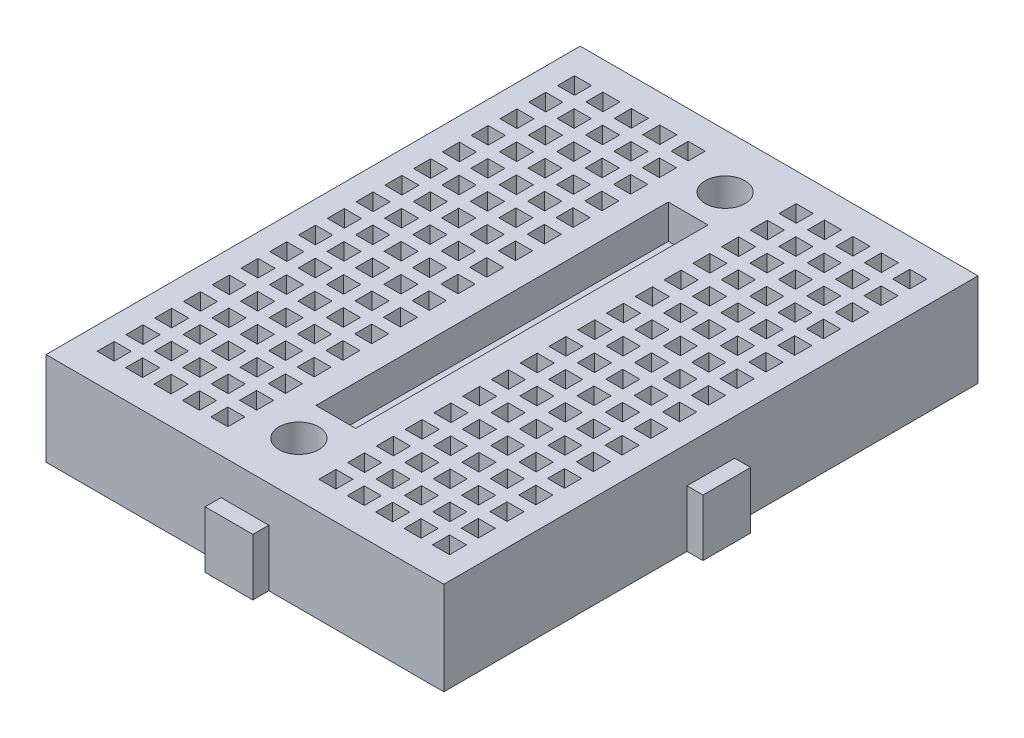
SolidWorks part; units mm, degrees
ref_plane "Front Plane" through (0, 0, 0) normal (0, 0, 1) x (1, 0, 0)
ref_plane "Top Plane" through (0, 0, 0) normal (0, 1, 0) x (1, 0, 0)
ref_plane "Right Plane" through (0, 0, 0) normal (1, 0, 0) x (0, 0, -1)
sketch "Sketch2" plane through (0, 0, 0) normal (0, 1, 0) x (1, 0, 0)
  line L1 (0, 23.5) -> (-17.5, 23.5)
  line L2 (0, 23.5) -> (0, -23.5)
  line L3 (0, -23.5) -> (-17.5, -23.5)
  line L4 (-17.5, 23.5) -> (-17.5, -23.5)
  line L5 (0, 23.5) -> (-17.5, -23.5) construction
  line L6 (0, -23.5) -> (-17.5, 23.5) construction
  point P0 (0, 0)
  point P7 (0, 0)
  dimension "D1" = 17.5
  dimension "D2" = 47
extrude "Boss-Extrude1" add sketch "Sketch2" along normal blind 5.2
sketch "Sketch3" plane through (0, 5.2, 0) normal (0, 1, 0) x (1, 0, 0)
  line L0 (0, -23.5) -> (0, 23.5) construction
  line L5 (1.75, -15.5) -> (-1.75, -15.5)
  line L6 (1.75, -15.5) -> (1.75, 15.5)
  line L7 (0, 23.5) -> (-17.5, 23.5) construction
  line L8 (-17.5, -23.5) -> (0, -23.5) construction
  line L9 (1.75, 15.5) -> (-1.75, 15.5)
  line L10 (-1.75, -15.5) -> (-1.75, 15.5)
  line L12 (-13, 21) -> (-13, 19.5)
  line L13 (-15.5, 21) -> (-14, 21)
  line L14 (-15.5, 21) -> (-15.5, 19.5)
  line L15 (-15.5, 19.5) -> (-14, 19.5)
  line L16 (-14, 21) -> (-14, 19.5)
  line L17 (-13, 21) -> (-11.5, 21)
  line L18 (-11.5, 21) -> (-11.5, 19.5)
  line L19 (-13, 19.5) -> (-11.5, 19.5)
  line L20 (-10.5, 21) -> (-10.5, 19.5)
  line L21 (-10.5, 21) -> (-9, 21)
  line L22 (-9, 21) -> (-9, 19.5)
  line L23 (-10.5, 19.5) -> (-9, 19.5)
  line L24 (-8, 21) -> (-8, 19.5)
  line L25 (-8, 21) -> (-6.5, 21)
  line L26 (-6.5, 21) -> (-6.5, 19.5)
  line L27 (-8, 19.5) -> (-6.5, 19.5)
  line L28 (-5.5, 21) -> (-5.5, 19.5)
  line L29 (-5.5, 21) -> (-4, 21)
  line L30 (-4, 21) -> (-4, 19.5)
  line L31 (-5.5, 19.5) -> (-4, 19.5)
  line L32 (-13, 18.4688) -> (-13, 16.9687)
  line L33 (-13, 18.4688) -> (-11.5, 18.4688)
  line L34 (-11.5, 18.4688) -> (-11.5, 16.9687)
  line L35 (-13, 16.9687) -> (-11.5, 16.9687)
  line L36 (-10.5, 18.4688) -> (-10.5, 16.9687)
  line L37 (-10.5, 18.4688) -> (-9, 18.4688)
  line L38 (-9, 18.4688) -> (-9, 16.9687)
  line L39 (-10.5, 16.9687) -> (-9, 16.9687)
  line L40 (-8, 18.4688) -> (-8, 16.9687)
  line L41 (-8, 18.4688) -> (-6.5, 18.4688)
  line L42 (-6.5, 18.4688) -> (-6.5, 16.9687)
  line L43 (-8, 16.9687) -> (-6.5, 16.9687)
  line L44 (-5.5, 18.4688) -> (-5.5, 16.9687)
  line L45 (-5.5, 18.4688) -> (-4, 18.4688)
  line L46 (-4, 18.4688) -> (-4, 16.9687)
  line L47 (-5.5, 16.9687) -> (-4, 16.9687)
  line L48 (-13, 15.9375) -> (-13, 14.4375)
  line L49 (-13, 15.9375) -> (-11.5, 15.9375)
  line L50 (-11.5, 15.9375) -> (-11.5, 14.4375)
  line L51 (-13, 14.4375) -> (-11.5, 14.4375)
  line L52 (-10.5, 15.9375) -> (-10.5, 14.4375)
  line L53 (-10.5, 15.9375) -> (-9, 15.9375)
  line L54 (-9, 15.9375) -> (-9, 14.4375)
  line L55 (-10.5, 14.4375) -> (-9, 14.4375)
  line L56 (-8, 15.9375) -> (-8, 14.4375)
  line L57 (-8, 15.9375) -> (-6.5, 15.9375)
  line L58 (-6.5, 15.9375) -> (-6.5, 14.4375)
  line L59 (-8, 14.4375) -> (-6.5, 14.4375)
  line L60 (-5.5, 15.9375) -> (-5.5, 14.4375)
  line L61 (-5.5, 15.9375) -> (-4, 15.9375)
  line L62 (-4, 15.9375) -> (-4, 14.4375)
  line L63 (-5.5, 14.4375) -> (-4, 14.4375)
  line L64 (-13, 13.4063) -> (-13, 11.9062)
  line L65 (-13, 13.4063) -> (-11.5, 13.4063)
  line L66 (-11.5, 13.4063) -> (-11.5, 11.9062)
  line L67 (-13, 11.9062) -> (-11.5, 11.9062)
  line L68 (-10.5, 13.4063) -> (-10.5, 11.9062)
  line L69 (-10.5, 13.4063) -> (-9, 13.4063)
  line L70 (-9, 13.4063) -> (-9, 11.9062)
  line L71 (-10.5, 11.9062) -> (-9, 11.9062)
  line L72 (-8, 13.4063) -> (-8, 11.9062)
  line L73 (-8, 13.4063) -> (-6.5, 13.4063)
  line L74 (-6.5, 13.4063) -> (-6.5, 11.9062)
  line L75 (-8, 11.9062) -> (-6.5, 11.9062)
  line L76 (-5.5, 13.4063) -> (-5.5, 11.9062)
  line L77 (-5.5, 13.4063) -> (-4, 13.4063)
  line L78 (-4, 13.4063) -> (-4, 11.9062)
  line L79 (-5.5, 11.9062) -> (-4, 11.9062)
  line L80 (-13, 10.875) -> (-13, 9.375)
  line L81 (-13, 10.875) -> (-11.5, 10.875)
  line L82 (-11.5, 10.875) -> (-11.5, 9.375)
  line L83 (-13, 9.375) -> (-11.5, 9.375)
  line L84 (-10.5, 10.875) -> (-10.5, 9.375)
  line L85 (-10.5, 10.875) -> (-9, 10.875)
  line L86 (-9, 10.875) -> (-9, 9.375)
  line L87 (-10.5, 9.375) -> (-9, 9.375)
  line L88 (-8, 10.875) -> (-8, 9.375)
  line L89 (-8, 10.875) -> (-6.5, 10.875)
  line L90 (-6.5, 10.875) -> (-6.5, 9.375)
  line L91 (-8, 9.375) -> (-6.5, 9.375)
  line L92 (-5.5, 10.875) -> (-5.5, 9.375)
  line L93 (-5.5, 10.875) -> (-4, 10.875)
  line L94 (-4, 10.875) -> (-4, 9.375)
  line L95 (-5.5, 9.375) -> (-4, 9.375)
  line L96 (-13, 8.3438) -> (-13, 6.8438)
  line L97 (-13, 8.3438) -> (-11.5, 8.3438)
  line L98 (-11.5, 8.3438) -> (-11.5, 6.8438)
  line L99 (-13, 6.8438) -> (-11.5, 6.8438)
  line L100 (-10.5, 8.3438) -> (-10.5, 6.8438)
  line L101 (-10.5, 8.3438) -> (-9, 8.3438)
  line L102 (-9, 8.3438) -> (-9, 6.8438)
  line L103 (-10.5, 6.8438) -> (-9, 6.8438)
  line L104 (-8, 8.3438) -> (-8, 6.8438)
  line L105 (-8, 8.3438) -> (-6.5, 8.3438)
  line L106 (-6.5, 8.3438) -> (-6.5, 6.8438)
  line L107 (-8, 6.8438) -> (-6.5, 6.8438)
  line L108 (-5.5, 8.3438) -> (-5.5, 6.8438)
  line L109 (-5.5, 8.3438) -> (-4, 8.3438)
  line L110 (-4, 8.3438) -> (-4, 6.8438)
  line L111 (-5.5, 6.8438) -> (-4, 6.8438)
  line L112 (-13, 5.8125) -> (-13, 4.3125)
  line L113 (-13, 5.8125) -> (-11.5, 5.8125)
  line L114 (-11.5, 5.8125) -> (-11.5, 4.3125)
  line L115 (-13, 4.3125) -> (-11.5, 4.3125)
  line L116 (-10.5, 5.8125) -> (-10.5, 4.3125)
  line L117 (-10.5, 5.8125) -> (-9, 5.8125)
  line L118 (-9, 5.8125) -> (-9, 4.3125)
  line L119 (-10.5, 4.3125) -> (-9, 4.3125)
  line L120 (-8, 5.8125) -> (-8, 4.3125)
  line L121 (-8, 5.8125) -> (-6.5, 5.8125)
  line L122 (-6.5, 5.8125) -> (-6.5, 4.3125)
  line L123 (-8, 4.3125) -> (-6.5, 4.3125)
  line L124 (-5.5, 5.8125) -> (-5.5, 4.3125)
  line L125 (-5.5, 5.8125) -> (-4, 5.8125)
  line L126 (-4, 5.8125) -> (-4, 4.3125)
  line L127 (-5.5, 4.3125) -> (-4, 4.3125)
  line L128 (-13, 3.2813) -> (-13, 1.7813)
  line L129 (-13, 3.2813) -> (-11.5, 3.2813)
  line L130 (-11.5, 3.2813) -> (-11.5, 1.7813)
  line L131 (-13, 1.7813) -> (-11.5, 1.7813)
  line L132 (-10.5, 3.2813) -> (-10.5, 1.7813)
  line L133 (-10.5, 3.2813) -> (-9, 3.2813)
  line L134 (-9, 3.2813) -> (-9, 1.7813)
  line L135 (-10.5, 1.7813) -> (-9, 1.7813)
  line L136 (-8, 3.2813) -> (-8, 1.7813)
  line L137 (-8, 3.2813) -> (-6.5, 3.2813)
  line L138 (-6.5, 3.2813) -> (-6.5, 1.7813)
  line L139 (-8, 1.7813) -> (-6.5, 1.7813)
  line L140 (-5.5, 3.2813) -> (-5.5, 1.7813)
  line L141 (-5.5, 3.2813) -> (-4, 3.2813)
  line L142 (-4, 3.2813) -> (-4, 1.7813)
  line L143 (-5.5, 1.7813) -> (-4, 1.7813)
  line L144 (-13, 0.75) -> (-13, -0.75)
  line L145 (-13, 0.75) -> (-11.5, 0.75)
  line L146 (-11.5, 0.75) -> (-11.5, -0.75)
  line L147 (-13, -0.75) -> (-11.5, -0.75)
  line L148 (-10.5, 0.75) -> (-10.5, -0.75)
  line L149 (-10.5, 0.75) -> (-9, 0.75)
  line L150 (-9, 0.75) -> (-9, -0.75)
  line L151 (-10.5, -0.75) -> (-9, -0.75)
  line L152 (-8, 0.75) -> (-8, -0.75)
  line L153 (-8, 0.75) -> (-6.5, 0.75)
  line L154 (-6.5, 0.75) -> (-6.5, -0.75)
  line L155 (-8, -0.75) -> (-6.5, -0.75)
  line L156 (-5.5, 0.75) -> (-5.5, -0.75)
  line L157 (-5.5, 0.75) -> (-4, 0.75)
  line L158 (-4, 0.75) -> (-4, -0.75)
  line L159 (-5.5, -0.75) -> (-4, -0.75)
  line L160 (-13, -1.7812) -> (-13, -3.2812)
  line L161 (-13, -1.7812) -> (-11.5, -1.7812)
  line L162 (-11.5, -1.7812) -> (-11.5, -3.2812)
  line L163 (-13, -3.2812) -> (-11.5, -3.2812)
  line L164 (-10.5, -1.7812) -> (-10.5, -3.2812)
  line L165 (-10.5, -1.7812) -> (-9, -1.7812)
  line L166 (-9, -1.7812) -> (-9, -3.2812)
  line L167 (-10.5, -3.2812) -> (-9, -3.2812)
  line L168 (-8, -1.7812) -> (-8, -3.2812)
  line L169 (-8, -1.7812) -> (-6.5, -1.7812)
  line L170 (-6.5, -1.7812) -> (-6.5, -3.2812)
  line L171 (-8, -3.2812) -> (-6.5, -3.2812)
  line L172 (-5.5, -1.7812) -> (-5.5, -3.2812)
  line L173 (-5.5, -1.7812) -> (-4, -1.7812)
  line L174 (-4, -1.7812) -> (-4, -3.2812)
  line L175 (-5.5, -3.2812) -> (-4, -3.2812)
  line L176 (-13, -4.3125) -> (-13, -5.8125)
  line L177 (-13, -4.3125) -> (-11.5, -4.3125)
  line L178 (-11.5, -4.3125) -> (-11.5, -5.8125)
  line L179 (-13, -5.8125) -> (-11.5, -5.8125)
  line L180 (-10.5, -4.3125) -> (-10.5, -5.8125)
  line L181 (-10.5, -4.3125) -> (-9, -4.3125)
  line L182 (-9, -4.3125) -> (-9, -5.8125)
  line L183 (-10.5, -5.8125) -> (-9, -5.8125)
  line L184 (-8, -4.3125) -> (-8, -5.8125)
  line L185 (-8, -4.3125) -> (-6.5, -4.3125)
  line L186 (-6.5, -4.3125) -> (-6.5, -5.8125)
  line L187 (-8, -5.8125) -> (-6.5, -5.8125)
  line L188 (-5.5, -4.3125) -> (-5.5, -5.8125)
  line L189 (-5.5, -4.3125) -> (-4, -4.3125)
  line L190 (-4, -4.3125) -> (-4, -5.8125)
  line L191 (-5.5, -5.8125) -> (-4, -5.8125)
  line L192 (-13, -6.8437) -> (-13, -8.3437)
  line L193 (-13, -6.8437) -> (-11.5, -6.8437)
  line L194 (-11.5, -6.8437) -> (-11.5, -8.3437)
  line L195 (-13, -8.3437) -> (-11.5, -8.3437)
  line L196 (-10.5, -6.8437) -> (-10.5, -8.3437)
  line L197 (-10.5, -6.8437) -> (-9, -6.8437)
  line L198 (-9, -6.8437) -> (-9, -8.3437)
  line L199 (-10.5, -8.3437) -> (-9, -8.3437)
  line L200 (-8, -6.8437) -> (-8, -8.3437)
  line L201 (-8, -6.8437) -> (-6.5, -6.8437)
  line L202 (-6.5, -6.8437) -> (-6.5, -8.3437)
  line L203 (-8, -8.3437) -> (-6.5, -8.3437)
  line L204 (-5.5, -6.8437) -> (-5.5, -8.3437)
  line L205 (-5.5, -6.8437) -> (-4, -6.8437)
  line L206 (-4, -6.8437) -> (-4, -8.3437)
  line L207 (-5.5, -8.3437) -> (-4, -8.3437)
  line L208 (-13, -9.375) -> (-13, -10.875)
  line L209 (-13, -9.375) -> (-11.5, -9.375)
  line L210 (-11.5, -9.375) -> (-11.5, -10.875)
  line L211 (-13, -10.875) -> (-11.5, -10.875)
  line L212 (-10.5, -9.375) -> (-10.5, -10.875)
  line L213 (-10.5, -9.375) -> (-9, -9.375)
  line L214 (-9, -9.375) -> (-9, -10.875)
  line L215 (-10.5, -10.875) -> (-9, -10.875)
  line L216 (-8, -9.375) -> (-8, -10.875)
  line L217 (-8, -9.375) -> (-6.5, -9.375)
  line L218 (-6.5, -9.375) -> (-6.5, -10.875)
  line L219 (-8, -10.875) -> (-6.5, -10.875)
  line L220 (-5.5, -9.375) -> (-5.5, -10.875)
  line L221 (-5.5, -9.375) -> (-4, -9.375)
  line L222 (-4, -9.375) -> (-4, -10.875)
  line L223 (-5.5, -10.875) -> (-4, -10.875)
  line L224 (-13, -11.9062) -> (-13, -13.4062)
  line L225 (-13, -11.9062) -> (-11.5, -11.9062)
  line L226 (-11.5, -11.9062) -> (-11.5, -13.4062)
  line L227 (-13, -13.4062) -> (-11.5, -13.4062)
  line L228 (-10.5, -11.9062) -> (-10.5, -13.4062)
  line L229 (-10.5, -11.9062) -> (-9, -11.9062)
  line L230 (-9, -11.9062) -> (-9, -13.4062)
  line L231 (-10.5, -13.4062) -> (-9, -13.4062)
  line L232 (-8, -11.9062) -> (-8, -13.4062)
  line L233 (-8, -11.9062) -> (-6.5, -11.9062)
  line L234 (-6.5, -11.9062) -> (-6.5, -13.4062)
  line L235 (-8, -13.4062) -> (-6.5, -13.4062)
  line L236 (-5.5, -11.9062) -> (-5.5, -13.4062)
  line L237 (-5.5, -11.9062) -> (-4, -11.9062)
  line L238 (-4, -11.9062) -> (-4, -13.4062)
  line L239 (-5.5, -13.4062) -> (-4, -13.4062)
  line L240 (-13, -14.4375) -> (-13, -15.9375)
  line L241 (-13, -14.4375) -> (-11.5, -14.4375)
  line L242 (-11.5, -14.4375) -> (-11.5, -15.9375)
  line L243 (-13, -15.9375) -> (-11.5, -15.9375)
  line L244 (-10.5, -14.4375) -> (-10.5, -15.9375)
  line L245 (-10.5, -14.4375) -> (-9, -14.4375)
  line L246 (-9, -14.4375) -> (-9, -15.9375)
  line L247 (-10.5, -15.9375) -> (-9, -15.9375)
  line L248 (-8, -14.4375) -> (-8, -15.9375)
  line L249 (-8, -14.4375) -> (-6.5, -14.4375)
  line L250 (-6.5, -14.4375) -> (-6.5, -15.9375)
  line L251 (-8, -15.9375) -> (-6.5, -15.9375)
  line L252 (-5.5, -14.4375) -> (-5.5, -15.9375)
  line L253 (-5.5, -14.4375) -> (-4, -14.4375)
  line L254 (-4, -14.4375) -> (-4, -15.9375)
  line L255 (-5.5, -15.9375) -> (-4, -15.9375)
  line L256 (-13, -16.9687) -> (-13, -18.4687)
  line L257 (-13, -16.9687) -> (-11.5, -16.9687)
  line L258 (-11.5, -16.9687) -> (-11.5, -18.4687)
  line L259 (-13, -18.4687) -> (-11.5, -18.4687)
  line L260 (-10.5, -16.9687) -> (-10.5, -18.4687)
  line L261 (-10.5, -16.9687) -> (-9, -16.9687)
  line L262 (-9, -16.9687) -> (-9, -18.4687)
  line L263 (-10.5, -18.4687) -> (-9, -18.4687)
  line L264 (-8, -16.9687) -> (-8, -18.4687)
  line L265 (-8, -16.9687) -> (-6.5, -16.9687)
  line L266 (-6.5, -16.9687) -> (-6.5, -18.4687)
  line L267 (-8, -18.4687) -> (-6.5, -18.4687)
  line L268 (-5.5, -16.9687) -> (-5.5, -18.4687)
  line L269 (-5.5, -16.9687) -> (-4, -16.9687)
  line L270 (-4, -16.9687) -> (-4, -18.4687)
  line L271 (-5.5, -18.4687) -> (-4, -18.4687)
  line L272 (-13, -19.5) -> (-13, -21)
  line L273 (-13, -19.5) -> (-11.5, -19.5)
  line L274 (-11.5, -19.5) -> (-11.5, -21)
  line L275 (-13, -21) -> (-11.5, -21)
  line L276 (-10.5, -19.5) -> (-10.5, -21)
  line L277 (-10.5, -19.5) -> (-9, -19.5)
  line L278 (-9, -19.5) -> (-9, -21)
  line L279 (-10.5, -21) -> (-9, -21)
  line L280 (-8, -19.5) -> (-8, -21)
  line L281 (-8, -19.5) -> (-6.5, -19.5)
  line L282 (-6.5, -19.5) -> (-6.5, -21)
  line L283 (-8, -21) -> (-6.5, -21)
  line L284 (-5.5, -19.5) -> (-5.5, -21)
  line L285 (-5.5, -19.5) -> (-4, -19.5)
  line L286 (-4, -19.5) -> (-4, -21)
  line L287 (-5.5, -21) -> (-4, -21)
  line L288 (-15.5, 18.4688) -> (-15.5, 16.9687)
  line L289 (-15.5, 18.4688) -> (-14, 18.4688)
  line L290 (-14, 18.4688) -> (-14, 16.9687)
  line L291 (-15.5, 16.9687) -> (-14, 16.9687)
  line L292 (-15.5, 15.9375) -> (-15.5, 14.4375)
  line L293 (-15.5, 15.9375) -> (-14, 15.9375)
  line L294 (-14, 15.9375) -> (-14, 14.4375)
  line L295 (-15.5, 14.4375) -> (-14, 14.4375)
  line L296 (-15.5, 13.4063) -> (-15.5, 11.9062)
  line L297 (-15.5, 13.4063) -> (-14, 13.4063)
  line L298 (-14, 13.4063) -> (-14, 11.9062)
  line L299 (-15.5, 11.9062) -> (-14, 11.9062)
  line L300 (-15.5, 10.875) -> (-15.5, 9.375)
  line L301 (-15.5, 10.875) -> (-14, 10.875)
  line L302 (-14, 10.875) -> (-14, 9.375)
  line L303 (-15.5, 9.375) -> (-14, 9.375)
  line L304 (-15.5, 8.3438) -> (-15.5, 6.8438)
  line L305 (-15.5, 8.3438) -> (-14, 8.3438)
  line L306 (-14, 8.3438) -> (-14, 6.8438)
  line L307 (-15.5, 6.8438) -> (-14, 6.8438)
  line L308 (-15.5, 5.8125) -> (-15.5, 4.3125)
  line L309 (-15.5, 5.8125) -> (-14, 5.8125)
  line L310 (-14, 5.8125) -> (-14, 4.3125)
  line L311 (-15.5, 4.3125) -> (-14, 4.3125)
  line L312 (-15.5, 3.2813) -> (-15.5, 1.7813)
  line L313 (-15.5, 3.2813) -> (-14, 3.2813)
  line L314 (-14, 3.2813) -> (-14, 1.7813)
  line L315 (-15.5, 1.7813) -> (-14, 1.7813)
  line L316 (-15.5, 0.75) -> (-15.5, -0.75)
  line L317 (-15.5, 0.75) -> (-14, 0.75)
  line L318 (-14, 0.75) -> (-14, -0.75)
  line L319 (-15.5, -0.75) -> (-14, -0.75)
  line L320 (-15.5, -1.7812) -> (-15.5, -3.2812)
  line L321 (-15.5, -1.7812) -> (-14, -1.7812)
  line L322 (-14, -1.7812) -> (-14, -3.2812)
  line L323 (-15.5, -3.2812) -> (-14, -3.2812)
  line L324 (-15.5, -4.3125) -> (-15.5, -5.8125)
  line L325 (-15.5, -4.3125) -> (-14, -4.3125)
  line L326 (-14, -4.3125) -> (-14, -5.8125)
  line L327 (-15.5, -5.8125) -> (-14, -5.8125)
  line L328 (-15.5, -6.8437) -> (-15.5, -8.3437)
  line L329 (-15.5, -6.8437) -> (-14, -6.8437)
  line L330 (-14, -6.8437) -> (-14, -8.3437)
  line L331 (-15.5, -8.3437) -> (-14, -8.3437)
  line L332 (-15.5, -9.375) -> (-15.5, -10.875)
  line L333 (-15.5, -9.375) -> (-14, -9.375)
  line L334 (-14, -9.375) -> (-14, -10.875)
  line L335 (-15.5, -10.875) -> (-14, -10.875)
  line L336 (-15.5, -11.9062) -> (-15.5, -13.4062)
  line L337 (-15.5, -11.9062) -> (-14, -11.9062)
  line L338 (-14, -11.9062) -> (-14, -13.4062)
  line L339 (-15.5, -13.4062) -> (-14, -13.4062)
  line L340 (-15.5, -14.4375) -> (-15.5, -15.9375)
  line L341 (-15.5, -14.4375) -> (-14, -14.4375)
  line L342 (-14, -14.4375) -> (-14, -15.9375)
  line L343 (-15.5, -15.9375) -> (-14, -15.9375)
  line L344 (-15.5, -16.9687) -> (-15.5, -18.4687)
  line L345 (-15.5, -16.9687) -> (-14, -16.9687)
  line L346 (-14, -16.9687) -> (-14, -18.4687)
  line L347 (-15.5, -18.4687) -> (-14, -18.4687)
  line L348 (-15.5, -19.5) -> (-15.5, -21)
  line L349 (-15.5, -19.5) -> (-14, -19.5)
  line L350 (-14, -19.5) -> (-14, -21)
  line L351 (-15.5, -21) -> (-14, -21)
  line L352 (-17.5, 23.5) -> (-17.5, -23.5) construction
  line L353 (-9.75, 21) -> (-9.75, 23.5) construction
  line L354 (-9.75, -21) -> (-9.75, -23.5) construction
  line L355 (1.75, -15.5) -> (-1.75, 15.5) construction
  line L356 (1.75, 15.5) -> (-1.75, -15.5) construction
  line L357 (0, 20.5) -> (0, 23.5) construction
  line L358 (0, 0) -> (-17.5, 0) construction
  circle A4 centre (0, 18.75) radius 1.75
  circle A5 centre (0, -18.75) radius 1.75
  point P0 (0, 0)
  point P1 (0, 0)
  point P36 (-4, 0)
  line M352 (-17.5, 23.5) -> (-17.5, -23.5)
  line M353 (-17.5, -23.5) -> (0, -23.5)
  line M354 (0, -23.5) -> (0, 23.5)
  line M355 (0, 23.5) -> (-17.5, 23.5)
  dimension "D3" = 3
  dimension "D4" = 31
  dimension "D2" = 3.5
  dimension "D5" = 3.5
  dimension "D6" = 1.5
  dimension "D9" = 11.5
  dimension "D10" = 42
  dimension "D11" = 2
  dimension "D7" = 5
  dimension "D8" = 17
extrude "Boss-Extrude2" add sketch "Sketch3" along normal blind 3 contours A4 L5 L10 L9 L351 L348 L349 L350 L347 L344 L345 L346 L343 L340 L341 L342 L339 L336 L337 L338 L335 L332 L333 L334 L331 L328 L329 L330 L327 L324 L325 L326 L323 L320 L321 L322 M354 M355 M352 M353 region at (-0.5015, 5.2, 16.25)
mirror "Mirror1" of "Boss-Extrude2", "Boss-Extrude1"
sketch "Sketch4" plane through (0, 5.2, 0) normal (0, 1, 0) x (1, 0, 0)
  circle A0 centre (0, 18.75) radius 1
  circle A1 centre (0, -18.75) radius 1
  dimension "D1" = 2
extrude "Cut-Extrude1" cut sketch "Sketch4" against normal through all
sketch "Sketch7" plane through (0, 0, 23.5) normal (0, 0, 1) x (1, 0, 0)
  line L0 (-17.5, 0) -> (17.5, 0) construction
  line L1 (2.1, 5) -> (-2.1, 5)
  line L2 (2.1, 5) -> (2.1, 0)
  line L3 (2.1, 0) -> (-2.1, 0)
  line L4 (-2.1, 5) -> (-2.1, 0)
  line L5 (2.1, 5) -> (-2.1, 0) construction
  line L6 (2.1, 0) -> (-2.1, 5) construction
  point P0 (0, 2.5)
  point P7 (0, 0)
  dimension "D1" = 4.2
  dimension "D2" = 5
extrude "Boss-Extrude4" add sketch "Sketch7" along normal blind 1.4
sketch "Sketch8" plane through (0, 0, -23.5) normal (0, 0, -1) x (-1, 0, 0)
  line L0 (-2.1, 5) -> (-2.1, 0) construction
  line L1 (-2.1, 0) -> (2.1, 0) construction
  line L2 (2.1, 5) -> (2.1, 0) construction
  line L3 (-2.1, 5) -> (2.1, 5) construction
  line L4 (-2.1, 5) -> (-2.1, 0)
  line L5 (-2.1, 0) -> (2.1, 0)
  line L6 (2.1, 5) -> (2.1, 0)
  line L7 (-2.1, 5) -> (2.1, 5)
extrude "Cut-Extrude2" cut sketch "Sketch8" against normal blind 1.7
sketch "Sketch9" plane through (17.5, 0, 0) normal (1, 0, 0) x (0, 0, -1)
  line L0 (23.5, 0) -> (-23.5, 0) construction
  line L1 (2.1, 5) -> (-2.1, 5)
  line L2 (2.1, 5) -> (2.1, 0)
  line L3 (2.1, 0) -> (-2.1, 0)
  line L4 (-2.1, 5) -> (-2.1, 0)
  line L5 (2.1, 5) -> (-2.1, 0) construction
  line L6 (2.1, 0) -> (-2.1, 5) construction
  point P0 (0, 2.5)
  point P8 (0, 0)
  dimension "D1" = 4.2
  dimension "D2" = 5
extrude "Boss-Extrude5" add sketch "Sketch9" along normal blind 1.4
sketch "Sketch10" plane through (-17.5, 0, 0) normal (-1, 0, 0) x (0, 0, 1)
  line L0 (-2.1, 0) -> (2.1, 0) construction
  line L1 (2.1, 5) -> (2.1, 0) construction
  line L2 (-2.1, 5) -> (-2.1, 0) construction
  line L3 (-2.1, 5) -> (2.1, 5) construction
  line L4 (-2.1, 0) -> (2.1, 0)
  line L5 (2.1, 5) -> (2.1, 0)
  line L6 (-2.1, 5) -> (-2.1, 0)
  line L7 (-2.1, 5) -> (2.1, 5)
extrude "Cut-Extrude3" cut sketch "Sketch10" against normal blind 1.7
